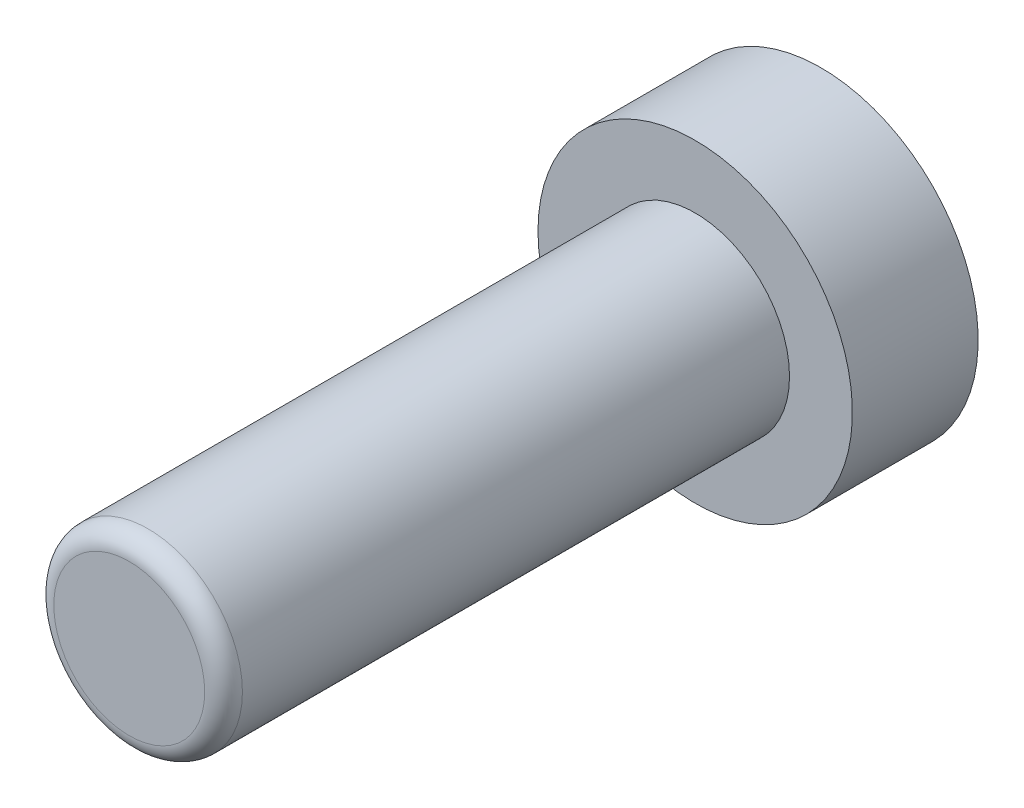
SolidWorks part; units mm, degrees
ref_plane "Front" through (0, 0, 0) normal (0, 0, 1) x (1, 0, 0)
ref_plane "Top" through (0, 0, 0) normal (0, 1, 0) x (1, 0, 0)
ref_plane "Right" through (0, 0, 0) normal (1, 0, 0) x (0, 0, -1)
sketch "Sketch1" plane through (0, 0, 0) normal (0, 0, 1) x (1, 0, 0)
  circle A0 centre (0, 0) radius 1.5
  dimension "D1" = 3
extrude "Boss-Extrude1" add sketch "Sketch1" along normal blind 9
sketch "Sketch2" plane through (0, 0, 0) normal (0, 0, -1) x (-1, 0, 0)
  circle A0 centre (0, 0) radius 2.5
  dimension "D1" = 5
extrude "Boss-Extrude2" add sketch "Sketch2" along normal blind 2
fillet "Fillet2" radius 0.3 1 edges at (1.5, 0, 9)
